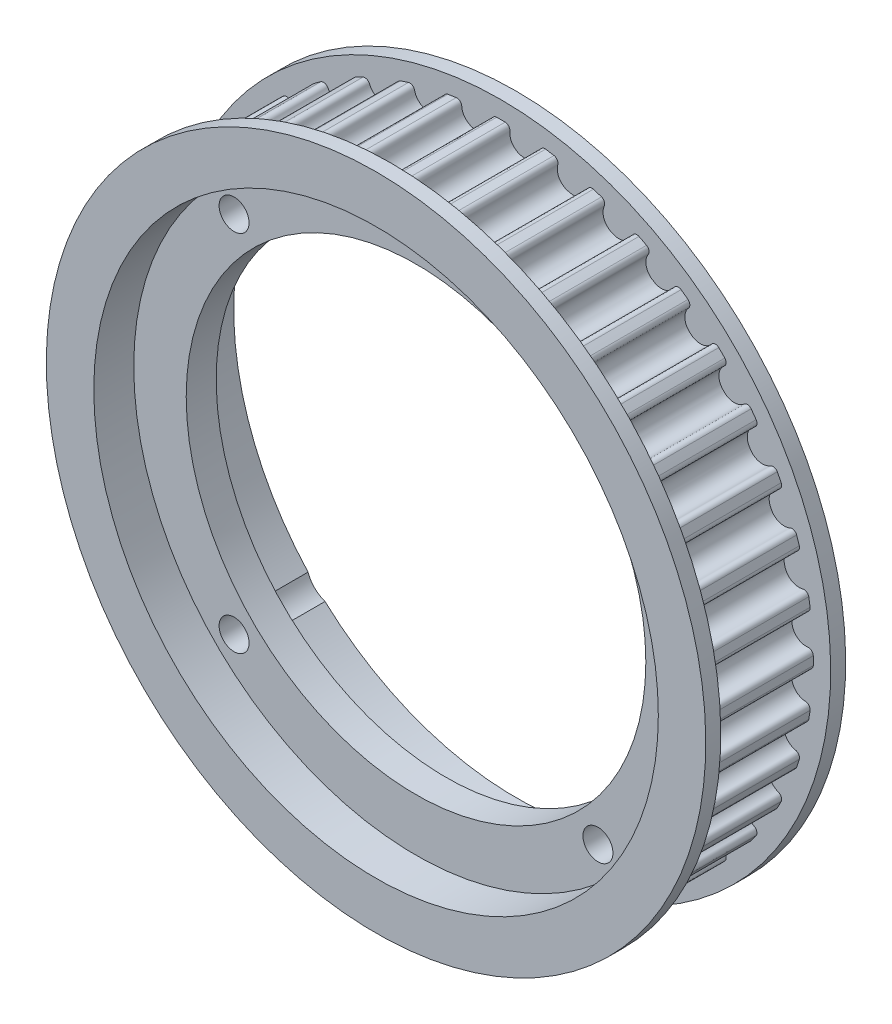
SolidWorks part; units mm, degrees
material "6061 合金"
ref_plane "前视基准面" through (0, 0, 0) normal (0, 0, 1) x (1, 0, 0)
ref_plane "上视基准面" through (0, 0, 0) normal (0, 1, 0) x (1, 0, 0)
ref_plane "右视基准面" through (0, 0, 0) normal (1, 0, 0) x (0, 0, -1)
ref_axis "基准轴1" through (0, 0, 55) along (0, 0, -1)
sketch "旋转草图同步带轮01" plane through (0, 0, 0) normal (1, 0, 0) x (0, 0, -1)
  line L0 (-7, 0) -> (-12.1779, 0) construction
  line L1 (7, 0) -> (7, 33)
  line L2 (7, 33) -> (5.5, 33)
  line L7 (5.5, 33) -> (5.5, 31.2595)
  line L8 (5.5, 31.2595) -> (-5.5, 31.2595)
  line L9 (-5.5, 31.2595) -> (-5.5, 33)
  line L14 (-5.5, 33) -> (-7, 33)
  line L15 (-7, 33) -> (-7, 0)
  line L16 (-7, 0) -> (7, 0)
  dimension "GearBeltOutsideDiameter" = 31.2595
  dimension "D1" = 11
  dimension "D2" = 1.5
  dimension "D3" = 66
revolve "同步带轮01" add sketch "旋转草图同步带轮01" angle 360 about L0
sketch "齿草图同步带轮01" plane through (0, 0, 0) normal (0, 0, 1) x (1, 0, 0)
  arc A0 (30.9369, 4.48) -> (31.2568, 0.4148) centre (0, 0) cw
  spline S0 degree 3 poles (31.2568, 0.4148) (31.2565, 0.4414) (31.2527, 0.4813) (31.2412, 0.5333) (31.2294, 0.5714) (31.2146, 0.6085) (31.1967, 0.6442) (31.176, 0.6784) (31.1526, 0.7107) (31.1266, 0.7411) (31.0982, 0.7692) (31.0677, 0.7949) (31.0351, 0.818) (31.0007, 0.8383) (30.9648, 0.8558) (30.9276, 0.8704) (30.8894, 0.8818) (30.8503, 0.89) (30.8107, 0.8951) (30.7708, 0.8969) (30.7237, 0.8948) (30.6526, 0.8881) (30.5568, 0.8842) (30.4439, 0.8887) (30.3317, 0.902) (30.2209, 0.9241) (30.1122, 0.9549) (30.0062, 0.994) (29.9036, 1.0414) (29.805, 1.0966) (29.7111, 1.1594) (29.6224, 1.2294) (29.5395, 1.3061) (29.4628, 1.3891) (29.3929, 1.4778) (29.3301, 1.5718) (29.2749, 1.6704) (29.2276, 1.773) (29.1885, 1.879) (29.1579, 1.9877) (29.1357, 2.0985) (29.1257, 2.1868) (29.1209, 2.2512) (29.1177, 2.2916) (29.1146, 2.332) (29.1092, 2.3964) (29.1053, 2.4851) (29.1099, 2.598) (29.1231, 2.7102) (29.1452, 2.8211) (29.1758, 2.9298) (29.2149, 3.0358) (29.2622, 3.1384) (29.3174, 3.237) (29.3801, 3.331) (29.45, 3.4197) (29.5267, 3.5027) (29.6096, 3.5794) (29.6983, 3.6494) (29.7923, 3.7122) (29.8908, 3.7675) (29.9934, 3.8148) (30.0994, 3.854) (30.2081, 3.8847) (30.3189, 3.9069) (30.4141, 3.918) (30.4854, 3.9225) (30.5322, 3.9277) (30.5714, 3.9358) (30.6097, 3.947) (30.647, 3.9612) (30.683, 3.9785) (30.7175, 3.9987) (30.7502, 4.0216) (30.781, 4.0471) (30.8095, 4.075) (30.8357, 4.1051) (30.8593, 4.1373) (30.8802, 4.1714) (30.8983, 4.207) (30.9134, 4.244) (30.9254, 4.282) (30.9343, 4.321) (30.94, 4.3605) (30.9432, 4.4137) (30.9407, 4.4536) (30.9369, 4.48) knots 0 0 0 0 0.012476 0.018713 0.024951 0.031189 0.037427 0.043665 0.049903 0.05614 0.062378 0.068616 0.074854 0.081092 0.08733 0.093567 0.099805 0.106043 0.112281 0.118519 0.124756 0.134376 0.152024 0.169672 0.18732 0.204968 0.222616 0.240264 0.257912 0.27556 0.293208 0.310856 0.328503 0.346151 0.363799 0.381447 0.399095 0.416743 0.434391 0.452039 0.469687 0.487335 0.493667 0.5 0.506333 0.512665 0.530313 0.547961 0.565609 0.583257 0.600905 0.618553 0.636201 0.653849 0.671497 0.689144 0.706792 0.72444 0.742088 0.759736 0.777384 0.795032 0.81268 0.830328 0.847976 0.865624 0.875244 0.881481 0.887719 0.893957 0.900195 0.906433 0.91267 0.918908 0.925146 0.931384 0.937622 0.94386 0.950097 0.956335 0.962573 0.968811 0.975049 0.981287 0.987524 1 1 1 1
extrude "齿拉伸切除同步带轮01" cut sketch "齿草图同步带轮01" against normal mid plane 11
pattern_circular "齿形同步带轮01" count 40 every 9 about axis through (0, 0, 55) along (0, 0, -1) of "齿拉伸切除同步带轮01"
sketch "孔旋转草图" plane through (0, 0, 0) normal (1, 0, 0) x (0, 0, -1)
  line L0 (0, 0) -> (1, 0) construction
  line L1 (-7.239, 0) -> (7.239, 0)
  line L2 (7.239, 0) -> (7.239, 25)
  line L3 (7.239, 25) -> (-7.239, 25)
  line L4 (-7.239, 25) -> (-7.239, 0)
  dimension "TaperSide1" = 25
  dimension "TaperSide2" = 25
revolve "孔旋转切除" [suppressed] cut sketch "孔旋转草图" angle 360 about L0
sketch "草图5" plane through (0, 0, 0) normal (0, 1, 0) x (1, 0, 0)
  circle A0 centre (0, 0) radius 2
  dimension "D1" = 4
extrude "切除-拉伸2" [suppressed] cut sketch "草图5" against normal blind 27
sketch "草图6" [suppressed] plane through (0, -27, 0) normal (0, 1, 0) x (1, 0, 0)
  circle A0 centre (0, 0) radius 3.9
  dimension "D1" = 7.8
extrude "切除-拉伸3" [suppressed] cut sketch "草图6" against normal through all
pattern_circular "阵列(圆周)2" [suppressed] count 3 every 90 reverse direction yes of bodies 110
sketch "草图7" plane through (0, 0, 7) normal (0, 0, 1) x (1, 0, 0)
  circle A0 centre (0, 0) radius 23
  circle A2 centre (0, 0) radius 25.75 construction
  circle A3 centre (-18.208, 18.208) radius 1.5
  circle A4 centre (18.208, 18.208) radius 1.5
  circle A5 centre (18.208, -18.208) radius 1.5
  circle A6 centre (-18.208, -18.208) radius 1.5
  dimension "D1" = 46
  dimension "D2" = 3
  dimension "D5" = 51.5
  dimension "D4" = 4
extrude "切除-拉伸4" cut sketch "草图7" against normal through all
sketch "草图10" plane through (0, 0, 7) normal (0, 0, 1) x (1, 0, 0)
  circle A0 centre (0, 0) radius 28.25
  circle A1 centre (0, 0) radius 23 construction
  dimension "D1" = 5.25
extrude "切除-拉伸5" cut sketch "草图10" against normal blind 4
sketch "草图11" plane through (0, 0, -7) normal (0, 0, -1) x (-1, 0, 0)
  circle A1 centre (0, 0) radius 28.25
  circle A2 centre (0, 0) radius 28.25 construction
extrude "切除-拉伸6" cut sketch "草图11" against normal blind 7
sketch "草图12" plane through (0, 0, -7) normal (0, 0, -1) x (-1, 0, 0)
  circle A0 centre (-18.208, 18.208) radius 2.75
  circle A1 centre (-18.208, -18.208) radius 2.75
  circle A2 centre (18.208, -18.208) radius 2.75
  circle A3 centre (18.208, 18.208) radius 2.75
  dimension "D1" = 5.5
extrude "切除-拉伸7" cut sketch "草图12" against normal up to surface (7 mm away) up to face at (0, 28.25, 0)
